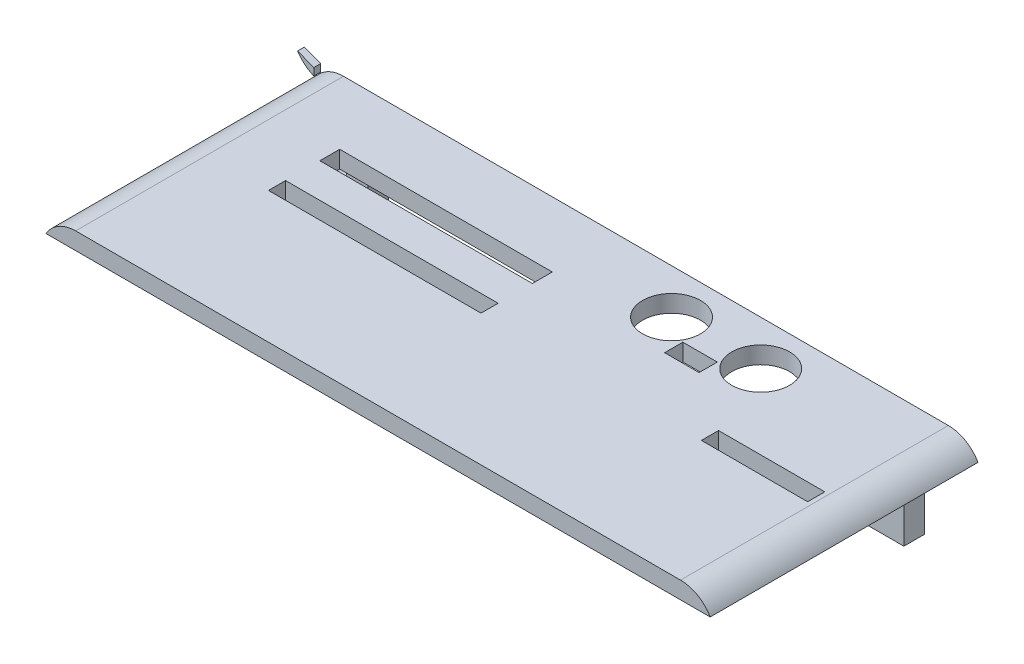
SolidWorks part; units mm, degrees
material "Aleación 1060"
ref_plane "Alzado" through (0, 0, 0) normal (0, 0, 1) x (1, 0, 0)
ref_plane "Planta" through (0, 0, 0) normal (0, 1, 0) x (1, 0, 0)
ref_plane "Vista lateral" through (0, 0, 0) normal (1, 0, 0) x (0, 0, -1)
sketch "Croquis2" plane through (0, 0, 0) normal (0, 0, 1) x (1, 0, 0)
  line L0 (64.1083, -69.3601) -> (64.1083, -63.6754) construction
  line L1 (-99.8917, -75.3601) -> (100.1083, -75.3601)
  line L2 (-99.8917, -75.3601) -> (-99.8917, 74.6399)
  line L3 (-99.8917, 74.6399) -> (100.1083, 74.6399)
  line L4 (100.1083, -75.3601) -> (100.1083, 74.6399)
  line L6 (100.1083, -69.3601) -> (-31.2492, -69.3601) construction
  line L7 (-32.0917, -69.3601) -> (-32.0917, -67.3601) construction
  line L8 (-62.0917, -69.3601) -> (-62.0917, -67.3601) construction
  line L11 (0.1083, -67.3601) -> (0.1083, -75.3601) construction
  line L15 (71.6083, -0.3601) -> (100.1083, -0.3601) construction
  line L34 (-99.8917, -0.3601) -> (-71.3917, -0.3601) construction
  line L35 (-62.0917, 70.6399) -> (64.1083, 70.6399)
  line L38 (-71.3917, -12.9024) -> (-71.3917, 12.1823)
  line L41 (-79.2417, -13.0101) -> (-71.3917, -12.9024)
  line L45 (92.1083, 45.4784) -> (92.1083, -46.1985)
  line L46 (89.1083, 45.8764) -> (89.1083, -46.5966)
  line L47 (84.1083, 12.2899) -> (84.1083, -13.0101)
  line L48 (84.1083, -13.0101) -> (79.4583, -13.0101)
  line L49 (71.6083, -13.0101) -> (71.6083, 12.2899)
  line L52 (79.4583, -13.0101) -> (71.6083, -13.0101)
  line L53 (84.1083, 12.2899) -> (79.4583, 12.2899)
  line L69 (-83.8917, -13.0101) -> (-79.2417, -13.0101)
  line L70 (-83.8917, 12.2899) -> (-83.8917, -13.0101)
  line L71 (-91.8917, 45.4784) -> (-91.8917, -46.1985)
  line L72 (-88.8917, 45.8764) -> (-88.8917, -46.5966)
  line L82 (79.4583, 12.2899) -> (71.6083, 12.2899)
  line L85 (-79.2417, 12.2899) -> (-71.3917, 12.1823)
  line L86 (-83.8917, 12.2899) -> (-79.2417, 12.2899)
  line L99 (-45.6601, 58.1834) -> (-14.3628, 58.1834)
  line L102 (64.1083, 66.6399) -> (-62.0917, 66.6399)
  line L103 (-62.0917, -71.3601) -> (64.1083, -71.3601)
  line L104 (64.1083, -67.3601) -> (-62.0917, -67.3601)
  line L118 (-45.6601, 58.1834) -> (-45.6601, 14.4146)
  line L119 (-45.6601, 14.4146) -> (-14.3628, 14.4146)
  line L120 (-14.3628, 58.1834) -> (-14.3628, 14.4146)
  line L121 (-45.6601, -4.9147) -> (-14.3628, -4.9147)
  line L122 (-45.6601, -4.9147) -> (-45.6601, -48.6834)
  line L123 (-45.6601, -48.6834) -> (-14.3628, -48.6834)
  line L124 (-14.3628, -4.9147) -> (-14.3628, -48.6834)
  line L125 (1.1959, 21.9686) -> (24.7698, 21.9686)
  line L126 (1.1959, 21.9686) -> (1.1959, -23.3553)
  line L127 (1.1959, -23.3553) -> (24.7698, -23.3553)
  line L128 (24.7698, 21.9686) -> (24.7698, -23.3553)
  circle A0 centre (89.1083, -66.5) radius 2
  arc A1 (64.1083, -71.3601) -> (64.1083, -67.3601) centre (64.1083, -69.3601) ccw
  arc A6 (-62.0917, -67.3601) -> (-62.0917, -71.3601) centre (-62.0917, -69.3601) ccw
  circle A8 centre (-88.8917, -66.5) radius 2
  arc A92 (89.1083, -46.5966) -> (92.1083, -46.1985) centre (90.6083, -46.3976) ccw
  arc A97 (-88.8917, -46.5966) -> (-91.8917, -46.1985) centre (-90.3917, -46.3976) cw
  arc A108 (-88.8917, 45.8764) -> (-91.8917, 45.4784) centre (-90.3917, 45.6774) ccw
  arc A109 (89.1083, 45.8764) -> (92.1083, 45.4784) centre (90.6083, 45.6774) cw
  circle A110 centre (89.1083, 65.7798) radius 2
  arc A113 (64.1083, 70.6399) -> (64.1083, 66.6399) centre (64.1083, 68.6399) cw
  arc A146 (-62.0917, 66.6399) -> (-62.0917, 70.6399) centre (-62.0917, 68.6399) cw
  circle A153 centre (-88.8917, 65.7798) radius 2
  circle A154 centre (-80.8654, -59.3601) radius 2.5
  circle A155 centre (81.1083, -59.3601) radius 2.5
  circle A156 centre (81.1083, 58.6399) radius 2.5
  circle A157 centre (-80.8654, 58.6399) radius 2.5
  point P0 (0, 0)
  point P78 (3.0535, -59.0858)
  point P80 (1.1959, -58.7698)
  point P84 (89.4782, -52.7527)
  point P89 (81.5012, -58.7833)
  point P95 (-80.8654, -59.3601)
  point P116 (-91.8917, -0.3601)
  point P120 (-5.0314, -61.027)
  point P121 (11.1384, -58.7698)
  point P128 (84.1083, -0.3601)
  point P135 (71.6083, -0.3601)
  point P139 (-71.3917, -0.3601)
  point P140 (-83.8917, -0.3601)
  point P143 (-88.8917, -0.3601)
  point P144 (0.0463, 58.5996)
  point P149 (89.1083, -0.3601)
  point P150 (92.1083, -0.3601)
  point P155 (81.5012, 58.0631)
  point P171 (49.6083, -0.3601)
  point P173 (46.6083, -0.3601)
  point P228 (1.1959, 58.2649)
  point P247 (7.6372, -0.3601)
  point P258 (-14.3628, -0.3601)
  point P290 (-80.8654, 58.38)
  dimension "D4" = 6
  dimension "D5" = 25
  dimension "D6" = 19.0263
  dimension "D7" = 16
  dimension "D9" = 16
  dimension "D19" = 26.8
  dimension "D32" = 8
  dimension "D22" = 3
  dimension "D8" = 19
  dimension "D1" = 200
  dimension "D2" = 150
  dimension "D10" = 11
  dimension "D11" = 11
  dimension "D35" = 12.65
  dimension "D36" = 5
  dimension "D42" = 4.65
  dimension "D43" = 12.5
extrude "Saliente-Extruir1" add sketch "Croquis2" along normal blind 2
fillet "Redondeo1" radius 10 4 edges at (-99.8917, 74.6399, 1) (-99.8917, -75.3601, 1) (100.1083, -75.3601, 1) (100.1083, 74.6399, 1)
sketch "Sketch1" plane through (0, 0, 2) normal (0, 0, 1) x (1, 0, 0)
  line L0 (-67.0718, 64.6399) -> (-67.0718, 60.6399)
  line L1 (-67.0718, 60.6399) -> (-8.8412, 60.6399)
  line L2 (-8.8412, 60.6399) -> (-8.8412, 3.6399)
  line L3 (-8.8412, 3.6399) -> (-67.0718, 3.6399)
  line L4 (-67.0718, 3.6399) -> (-67.0718, -0.3601)
  line L5 (-67.0718, -0.3601) -> (-8.8412, -0.3601)
  line L6 (-8.8412, -0.3601) -> (-8.8412, -53.3601)
  line L7 (-8.8412, -53.3601) -> (-67.0718, -53.3601)
  line L8 (-67.0718, -53.3601) -> (-67.0718, -57.5747)
  line L9 (-67.0718, -57.5747) -> (-5.0314, -57.5747)
  line L10 (-5.0314, -57.5747) -> (-5.0314, -40.9314)
  line L11 (-5.0314, -40.9314) -> (46.6083, -40.9314)
  line L12 (46.6083, -40.9314) -> (46.6083, -36.9314)
  line L13 (46.6083, -36.9314) -> (-5.0314, -36.9314)
  line L14 (-5.0314, -36.9314) -> (-5.0314, 30.0686)
  line L15 (-5.0314, 30.0686) -> (46.6083, 30.0686)
  line L16 (46.6083, 30.0686) -> (46.6083, 34.0686)
  line L17 (46.6083, 34.0686) -> (-5.0314, 34.0686)
  line L18 (-5.0314, 34.0686) -> (-5.0314, 64.6399)
  line L19 (-5.0314, 64.6399) -> (-67.0718, 64.6399)
extrude "Boss-Extrude1" add sketch "Sketch1" along normal blind 25
sketch "Sketch3" plane through (0, -57.5747, 0) normal (0, -1, 0) x (1, 0, 0)
  line L0 (-5.0314, 27) -> (-5.0314, 2) construction
  line L1 (-67.0718, 27) -> (-5.0314, 27)
  line L2 (-67.0718, 27) -> (-67.0718, 21.4692)
  line L3 (-67.0718, 21.4692) -> (-5.0314, 21.4692)
  line L4 (-5.0314, 27) -> (-5.0314, 21.4692)
extrude "Boss-Extrude2" add sketch "Sketch3" along normal blind 22
sketch "Sketch8" plane through (0, 64.6399, 0) normal (0, 1, 0) x (1, 0, 0)
  line L0 (-67.0718, -21.4692) -> (-5.0314, -21.4692)
  line L1 (-5.0314, -27) -> (-5.0314, -2) construction
  line L2 (-5.0314, -21.4692) -> (-5.0314, -27)
  line L3 (-5.0314, -27) -> (-67.0718, -27)
  line L4 (-67.0718, -27) -> (-67.0718, -21.4692)
extrude "Boss-Extrude6" add sketch "Sketch8" along normal blind 13
sketch "Sketch2" plane through (0, -75.3601, 0) normal (0, -1, 0) x (1, 0, 0)
  line L1 (-93.6501, 2) -> (100.1083, 2)
  line L2 (-93.6501, 2) -> (-93.6501, 80.1241)
  line L3 (-93.6501, 80.1241) -> (100.1083, 80.1241)
  line L4 (100.1083, 2) -> (100.1083, 80.1241)
  line L5 (-67.0718, 27) -> (-5.0314, 27)
  line L6 (-67.0718, 27) -> (-67.0718, 21.4692)
  line L7 (-67.0718, 21.4692) -> (-5.0314, 21.4692)
  line L8 (-5.0314, 27) -> (-5.0314, 21.4692)
extrude "Boss-Extrude3" add sketch "Sketch2" against normal blind 5
sketch "Sketch4" plane through (0, 64.6399, 0) normal (0, 1, 0) x (1, 0, 0)
  line L1 (-67.0718, -21.4692) -> (-5.0314, -21.4692)
  line L2 (-67.0718, -21.4692) -> (-67.0718, -27)
  line L3 (-67.0718, -27) -> (-5.0314, -27)
  line L4 (-5.0314, -21.4692) -> (-5.0314, -27)
extrude "Boss-Extrude4" add sketch "Sketch4" along normal blind 19
sketch "Sketch5" plane through (0, -75.3601, 0) normal (0, -1, 0) x (1, 0, 0)
  line L0 (0.1083, 80.1241) -> (0.1083, 0) construction
  line L1 (-84.2615, 2) -> (-76.8189, 2)
  line L2 (-84.2615, 2) -> (-84.2615, 4.9915)
  line L3 (-84.2615, 4.9915) -> (-76.8189, 4.9915)
  line L4 (-76.8189, 2) -> (-76.8189, 4.9915)
  line L5 (100.1083, 80.1241) -> (-93.6501, 80.1241) construction
  line L6 (-89.8917, 0) -> (90.1083, 0) construction
  line L7 (100.1083, 2) -> (100.1083, 80.1241) construction
  line L8 (84.478, 2) -> (84.478, 4.9915)
  line L9 (84.478, 2) -> (77.0354, 2)
  line L10 (77.0354, 2) -> (77.0354, 4.9915)
  line L11 (84.478, 4.9915) -> (77.0354, 4.9915)
  dimension "D1" = 100
extrude "Boss-Extrude5" add sketch "Sketch5" along normal blind 21
sketch "Sketch6" plane through (0, 0, 4.9915) normal (0, 0, 1) x (1, 0, 0)
  line L0 (0, 0) -> (3.2291, -75.3601) construction
  line L1 (100.1083, -75.3601) -> (-93.6501, -75.3601) construction
  line L2 (100.1083, -70.3601) -> (-93.6501, -70.3601) construction
  line L3 (-106.505, 85.8914) -> (-93.5665, 85.8914)
  line L4 (-106.505, 85.8914) -> (-106.505, -70.3601)
  line L5 (-106.505, -70.3601) -> (-99.135, -70.3601)
  line L6 (-93.5665, 85.8914) -> (-93.5665, -70.3601)
  line L8 (-99.135, -70.3601) -> (-93.6501, -72.4856)
  line L9 (-93.6501, -70.3601) -> (-93.6501, -75.3601) construction
  line L10 (-93.6501, -72.4856) -> (-93.6501, -70.3601)
  line L11 (-93.6501, -70.3601) -> (-93.5665, -70.3601)
  circle A0 centre (-80.996, -59.2843) radius 2.5
  circle A1 centre (85.7703, -52.1387) radius 2.5
extrude "Cut-Extrude1" cut sketch "Sketch6" against normal through all
fillet "Fillet1" radius 10 2 edges at (100.1083, -70.3601, 41.0621) (-93.6501, -70.3601, 40.0621)
sketch "Sketch11" plane through (0, -75.3601, 0) normal (0, -1, 0) x (1, 0, 0)
  line L1 (-67.0917, 26.7915) -> (-5.0917, 26.7915)
  line L2 (-67.0917, 26.7915) -> (-67.0917, 20.9915)
  line L3 (-67.0917, 20.9915) -> (-5.0917, 20.9915)
  line L4 (-5.0917, 26.7915) -> (-5.0917, 20.9915)
  line L5 (-84.2615, 4.9915) -> (-76.8189, 4.9915) construction
  line L6 (-67.0917, 36.7915) -> (-5.0917, 36.7915)
  line L7 (-93.6501, 2) -> (100.1083, 2)
  line L8 (-93.6501, 2) -> (-93.6501, 0)
  line L9 (-93.6501, 0) -> (100.1083, 0)
  line L10 (100.1083, 2) -> (100.1083, 0)
  line L11 (-67.0917, 36.7915) -> (-67.0917, 41.7915)
  line L12 (-67.0917, 41.7915) -> (-5.0917, 41.7915)
  line L13 (-5.0917, 36.7915) -> (-5.0917, 41.7915)
  line L14 (59.2083, 36.7915) -> (86.5083, 36.7915)
  line L15 (59.2083, 36.7915) -> (59.2083, 41.7915)
  line L16 (59.2083, 41.7915) -> (86.5083, 41.7915)
  line L17 (86.5083, 36.7915) -> (86.5083, 41.7915)
  dimension "D1" = 5
  dimension "D2" = 62
  dimension "D3" = 16
  dimension "D4" = 5.8
  dimension "D5" = 10
  dimension "D6" = 27.3
  dimension "D7" = 64.3
sketch "Sketch13" plane through (0, 0, 27) normal (0, 0, 1) x (1, 0, 0)
  line L1 (-67.0718, -75.3601) -> (-5.0314, -75.3601)
  line L2 (-67.0718, -75.3601) -> (-67.0718, -79.5747)
  line L3 (-67.0718, -79.5747) -> (-5.0314, -79.5747)
  line L4 (-5.0314, -75.3601) -> (-5.0314, -79.5747)
extrude "Cut-Extrude6" cut sketch "Sketch13" against normal through all
sketch "Sketch14" plane through (0, 0, 4.9915) normal (0, 0, 1) x (1, 0, 0)
  circle A0 centre (-80.5944, -88.2423) radius 2.5
  circle A1 centre (80.7469, -88.2423) radius 2.5
  dimension "D1" = 5
  dimension "D2" = 5
extrude "Cut-Extrude7" cut sketch "Sketch14" against normal through all
extrude "Cut-Extrude8" cut sketch "Sketch11" against normal through all
sketch "Sketch17" plane through (0, 0, 27) normal (0, 0, 1) x (1, 0, 0)
  line L0 (91.448, -70.3601) -> (-84.9899, -70.3601) construction
  line L1 (-79.3341, 87.1853) -> (50.8272, 87.1853)
  line L2 (-79.3341, 87.1853) -> (-79.3341, -70.3601)
  line L3 (-79.3341, -70.3601) -> (50.8272, -70.3601)
  line L4 (50.8272, 87.1853) -> (50.8272, -70.3601)
extrude "Cut-Extrude9" cut sketch "Sketch17" against normal through all
sketch "Sketch18" [suppressed] plane through (0, -75.3601, 0) normal (0, -1, 0) x (1, 0, 0)
  line L0 (100.1083, 80.1241) -> (-99.8917, 80.1241) construction
  line L1 (-4.4843, 40.2045) -> (4.4843, 40.2045)
  line L2 (-4.4843, 40.2045) -> (-4.4843, 53.4566)
  line L3 (-4.4843, 53.4566) -> (4.4843, 53.4566)
  line L4 (4.4843, 40.2045) -> (4.4843, 53.4566)
  line L5 (-4.4843, 40.2045) -> (4.4843, 53.4566) construction
  line L6 (-4.4843, 53.4566) -> (4.4843, 40.2045) construction
  line L7 (-99.8917, 80.1241) -> (-99.8917, 2) construction
  point P0 (0, 46.8306)
  dimension "D1" = 33.2936
  dimension "D2" = 8.9686
  dimension "D3" = 95.4074
extrude "Cut-Extrude10" [suppressed] cut sketch "Sketch18" against normal blind 2
sketch "Croquis5" plane through (0, -75.3601, 0) normal (0, -1, 0) x (1, 0, 0)
  line L0 (-5.0917, 41.7915) -> (59.2083, 41.7915) construction
  line L2 (86.5083, 41.7915) -> (90.2083, 41.7915)
  line L3 (86.5083, 41.7915) -> (86.5083, 36.7915)
  line L4 (86.5083, 36.7915) -> (90.2083, 36.7915)
  line L5 (90.2083, 41.7915) -> (90.2083, 36.7915)
  dimension "D1" = 64.3
  dimension "D2" = 3.7
extrude "Cortar-Extruir7" cut sketch "Croquis5" against normal blind 10
sketch "Croquis6" plane through (-76.8189, 0, 0) normal (1, 0, 0) x (0, 0, -1)
  line L1 (-4.9915, -75.3601) -> (-2, -75.3601)
  line L2 (-4.9915, -75.3601) -> (-4.9915, -96.3601)
  line L3 (-4.9915, -96.3601) -> (-2, -96.3601)
  line L4 (-2, -75.3601) -> (-2, -96.3601)
extrude "Saliente-Extruir2" add sketch "Croquis6" along normal blind 5
sketch "Croquis7" plane through (0, -96.3601, 0) normal (0, -1, 0) x (1, 0, 0)
  line L1 (-84.2615, 4.9915) -> (-71.8189, 4.9915)
  line L2 (-84.2615, 4.9915) -> (-84.2615, 2)
  line L3 (-84.2615, 2) -> (-71.8189, 2)
  line L4 (-71.8189, 4.9915) -> (-71.8189, 2)
extrude "Saliente-Extruir3" add sketch "Croquis7" along normal blind 5
sketch "Croquis8" plane through (0, 0, 4.9915) normal (0, 0, 1) x (1, 0, 0)
  line L1 (-71.8189, -101.3601) -> (-84.2615, -101.3601)
  line L2 (-71.8189, -101.3601) -> (-71.8189, -75.3601)
  line L3 (-71.8189, -75.3601) -> (-84.2615, -75.3601)
  line L4 (-84.2615, -101.3601) -> (-84.2615, -75.3601)
extrude "Saliente-Extruir4" add sketch "Croquis8" along normal blind 3
sketch "Croquis9" plane through (0, 0, 2) normal (0, 0, -1) x (-1, 0, 0)
  circle A0 centre (80.5944, -88.2423) radius 2.5
extrude "Cortar-Extruir8" cut sketch "Croquis9" against normal blind 16
sketch "Croquis11" plane through (77.0354, 0, 0) normal (-1, 0, 0) x (0, 0, 1)
  line L1 (4.9915, -96.3601) -> (2, -96.3601)
  line L2 (4.9915, -96.3601) -> (4.9915, -75.3601)
  line L3 (4.9915, -75.3601) -> (2, -75.3601)
  line L4 (2, -96.3601) -> (2, -75.3601)
extrude "Saliente-Extruir5" add sketch "Croquis11" along normal blind 5
sketch "Croquis12" plane through (0, -96.3601, 0) normal (0, -1, 0) x (1, 0, 0)
  line L1 (72.0354, 4.9915) -> (84.478, 4.9915)
  line L2 (72.0354, 4.9915) -> (72.0354, 2)
  line L3 (72.0354, 2) -> (84.478, 2)
  line L4 (84.478, 4.9915) -> (84.478, 2)
extrude "Saliente-Extruir6" add sketch "Croquis12" along normal blind 5
sketch "Croquis13" plane through (0, 0, 4.9915) normal (0, 0, 1) x (1, 0, 0)
  line L1 (84.478, -101.3601) -> (72.0354, -101.3601)
  line L2 (84.478, -101.3601) -> (84.478, -75.3601)
  line L3 (84.478, -75.3601) -> (72.0354, -75.3601)
  line L4 (72.0354, -101.3601) -> (72.0354, -75.3601)
extrude "Saliente-Extruir7" add sketch "Croquis13" along normal blind 3
sketch "Croquis14" plane through (0, 0, 2) normal (0, 0, -1) x (-1, 0, 0)
  circle A0 centre (-80.7469, -88.2423) radius 2.5
extrude "Cortar-Extruir9" cut sketch "Croquis14" against normal blind 15
sketch "Croquis15" plane through (0, -70.3601, 0) normal (0, 1, 0) x (1, 0, 0)
  line L0 (41.7309, -19.6773) -> (31.6857, -19.6773)
  line L10 (31.6857, -19.6773) -> (31.6857, -25)
  line L11 (41.7309, -24.9973) -> (31.6857, -24.9973)
  line L12 (41.7309, -24.9973) -> (41.7309, -19.6773)
  line L13 (41.7309, -19.6773) -> (31.6857, -19.6773)
  line L14 (31.6857, -24.9973) -> (31.6857, -19.6773)
  line L15 (59.2083, -5) -> (59.2083, -15) construction
  line L16 (59.2083, -5) -> (49.7083, -5) construction
  line L17 (59.2083, -25) -> (14.2083, -25)
  line L18 (59.2083, -25) -> (59.2083, -5)
  line L19 (59.2083, -5) -> (14.2083, -5)
  line L20 (14.2083, -25) -> (14.2083, -5)
  line L21 (59.2083, -15) -> (49.7083, -15) construction
  line L22 (49.7083, -15) -> (49.7083, -5) construction
  line L23 (14.2083, -15) -> (23.7083, -15) construction
  line L24 (59.2083, -25) -> (59.2083, -22.34) construction
  line L25 (59.2083, -22.34) -> (41.7309, -22.34) construction
  line L27 (41.7309, -24.9973) -> (41.7309, -19.6773)
  circle A4 centre (49.7083, -15) radius 8.45
  circle A5 centre (23.7083, -15) radius 8.45
  dimension "D3" = 16.9
  dimension "D5" = 16.9
  dimension "D1" = 10
  dimension "D2" = 9.5
  dimension "D4" = 9.5
  dimension "D6" = 2.66
extrude "Cortar-Extruir10" cut sketch "Croquis15" against normal blind 15 contours L11 L12 L0 L10 | A4 | A5 region at (36.7083, -70.3601, 22.3373) region at (49.7083, -70.3601, 15) region at (23.7083, -70.3601, 15)
